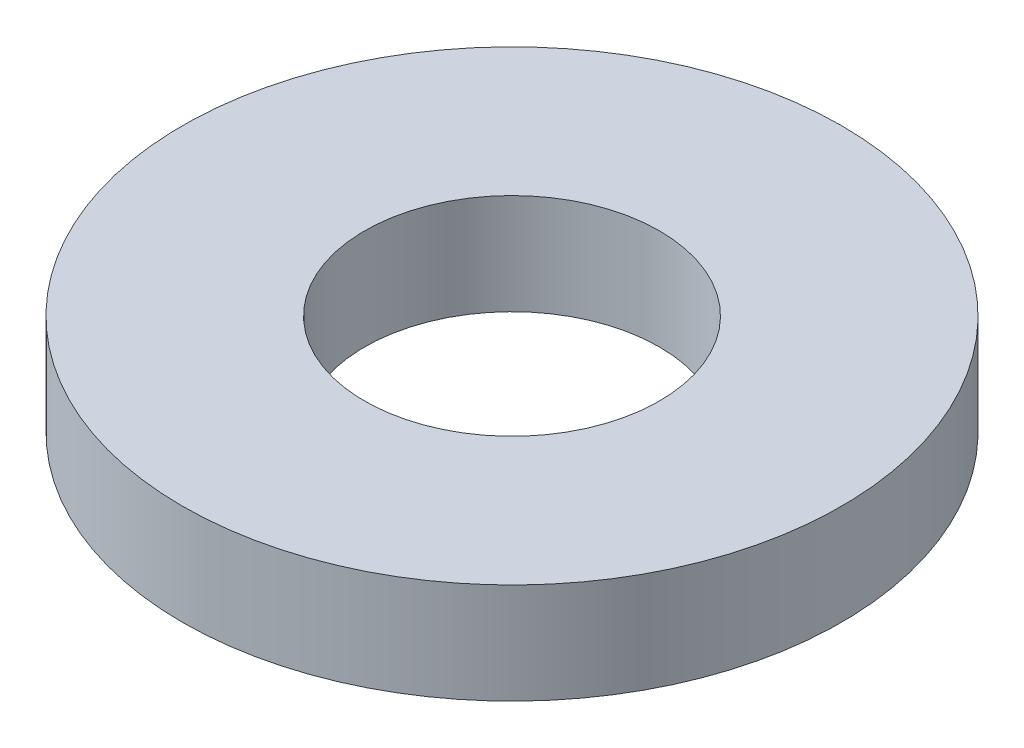
SolidWorks part; units mm, degrees
ref_plane "Front Plane" through (0, 0, 0) normal (0, 0, 1) x (1, 0, 0)
ref_plane "Top Plane" through (0, 0, 0) normal (0, 1, 0) x (1, 0, 0)
ref_plane "Right Plane" through (0, 0, 0) normal (1, 0, 0) x (0, 0, -1)
sketch "Sketch1" plane through (0, 0, 0) normal (0, 1, 0) x (1, 0, 0)
  circle A0 centre (0, 0) radius 95
  dimension "FLANGE_OD" = 190
extrude "Boss-Extrude1" add sketch "Sketch1" along normal blind 29
sketch "Sketch2" plane through (0, 0, 0) normal (0, 1, 0) x (1, 0, 0)
  circle A0 centre (0, 0) radius 42.5
  dimension "BORE_D" = 85
extrude "Cut-Extrude1" cut sketch "Sketch2" along normal through all
sketch "Sketch3" plane through (0, 29, 0) normal (0, 1, 0) x (1, 0, 0)
  circle A0 centre (0, 0) radius 40.3388 construction
  circle A1 centre (-40.3388, 0) radius 1.6967
  dimension "BOLT_D" = 3.3934
  dimension "BOLT_PCD" = 80.6775
extrude "Cut-Extrude2" cut sketch "Sketch3" against normal blind 20.0901 rebuild error yes
pattern_circular "CirPattern1" count 5 over 360 rebuild error yes
